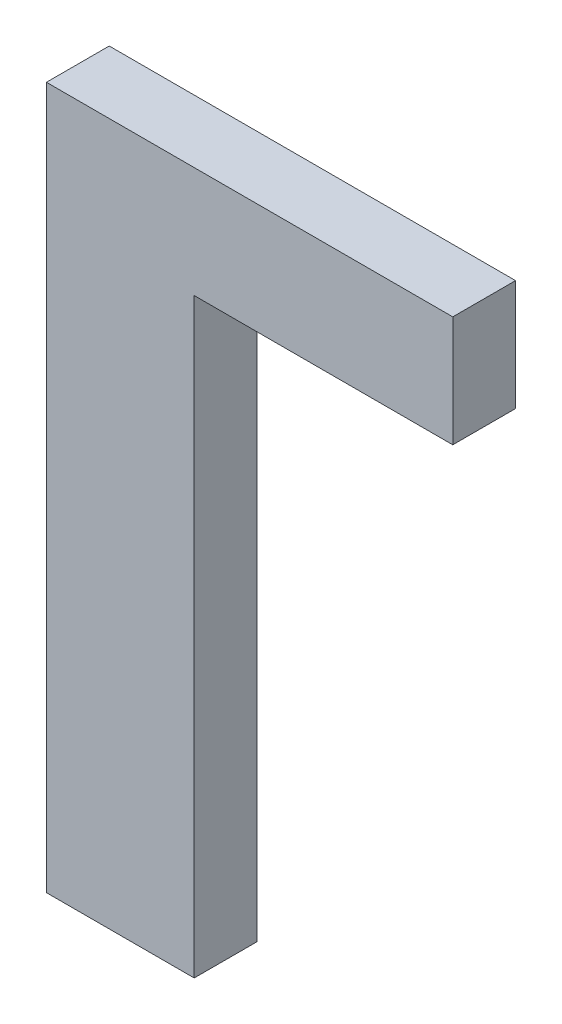
SolidWorks part; units mm, degrees
ref_plane "Front Plane" through (0, 0, 0) normal (0, 0, 1) x (1, 0, 0)
ref_plane "Top Plane" through (0, 0, 0) normal (0, 1, 0) x (1, 0, 0)
ref_plane "Right Plane" through (0, 0, 0) normal (1, 0, 0) x (0, 0, -1)
sketch "Sketch1" plane through (0, 0, 0) normal (0, 0, 1) x (1, 0, 0)
  line L1 (-5.08, 24.13) -> (5.08, 24.13)
  line L2 (-5.08, 24.13) -> (-5.08, -24.13)
  line L3 (-5.08, -24.13) -> (5.08, -24.13)
  line L4 (5.08, 24.13) -> (5.08, -24.13)
  line L5 (-5.08, 24.13) -> (5.08, -24.13) construction
  line L6 (-5.08, -24.13) -> (5.08, 24.13) construction
  point P0 (0, 0)
  dimension "D1" = 10.16
  dimension "D2" = 48.26
extrude "Boss-Extrude1" add sketch "Sketch1" along normal blind 4.318
sketch "Sketch2" plane through (5.08, 0, 0) normal (1, 0, 0) x (0, 0, -1)
  line L0 (0, -24.13) -> (0, 24.13) construction
  line L1 (-4.318, 24.13) -> (0, 24.13)
  line L2 (-4.318, 24.13) -> (-4.318, 16.51)
  line L3 (-4.318, 16.51) -> (0, 16.51)
  line L4 (0, 24.13) -> (0, 16.51)
  dimension "D1" = 7.62
extrude "Boss-Extrude2" add sketch "Sketch2" along normal blind 17.78
